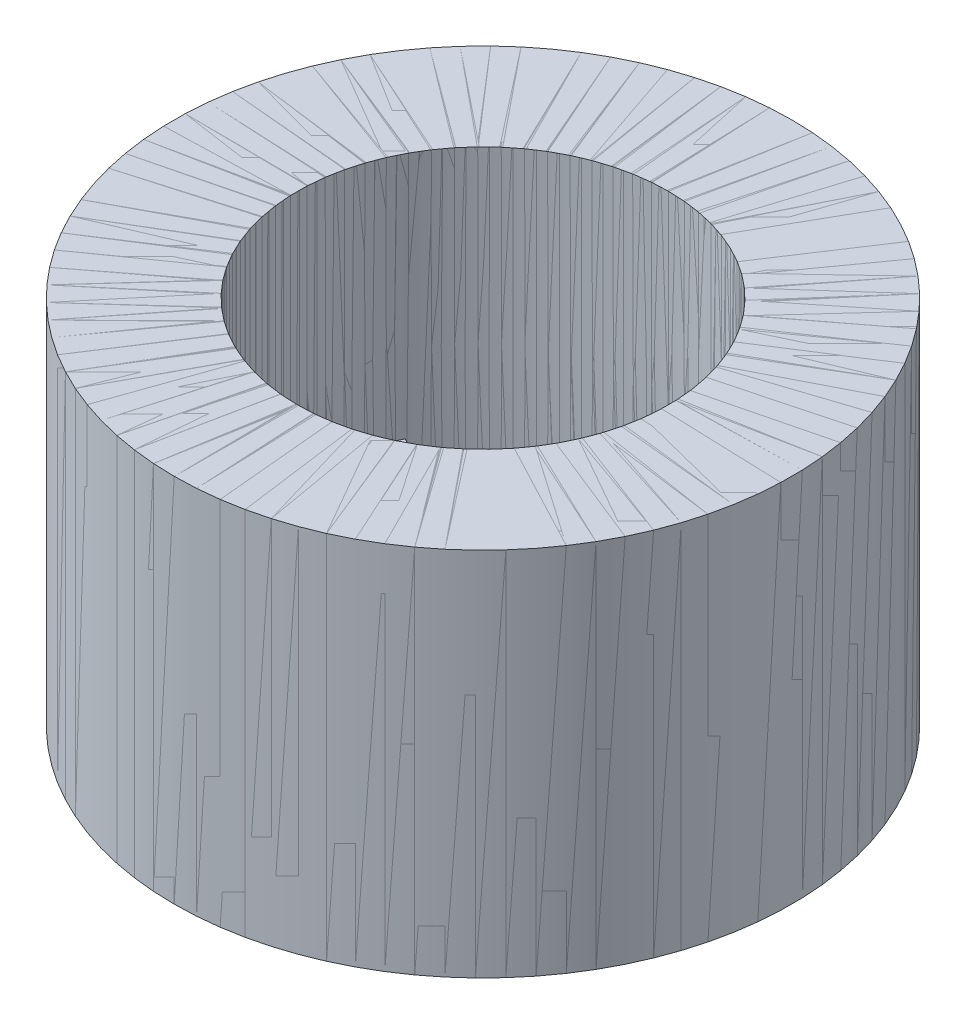
SolidWorks part; units mm, degrees
ref_plane "Front Plane" through (0, 0, 0) normal (0, 0, 1) x (1, 0, 0)
ref_plane "Top Plane" through (0, 0, 0) normal (0, 1, 0) x (1, 0, 0)
ref_plane "Right Plane" through (0, 0, 0) normal (1, 0, 0) x (0, 0, -1)
sketch "Sketch1" plane through (0, 0, 0) normal (0, 1, 0) x (1, 0, 0)
  line L2 (-2.5316, 14.7848) -> (-1.5, 9.2848)
  line L4 (1.451, 4.7848) -> (1.5, 9.2848)
  line L5 (1.5, 9.2848) -> (2.5316, 14.7848)
  line L6 (-1.5, 9.2848) -> (-1.451, 4.7848)
  line L7 (0, -55) -> (0, 55) construction
  circle A0 centre (0, 0) radius 15
  circle A1 centre (0, 0) radius 25
  arc A2 (-2.5316, 14.7848) -> (2.5316, 14.7848) centre (0, 0) cw
  circle A3 centre (0, 0) radius 5
  arc A4 (-1.451, 4.7848) -> (1.451, 4.7848) centre (0, 0) cw
  circle A5 centre (0, 0) radius 3
  dimension "D1" = 30
  dimension "D2" = 50
  dimension "D3" = 6
  dimension "D4" = 10
  dimension "D5" = 5
  dimension "D6" = 5.5
  dimension "D7" = 4.5
  dimension "D8" = 170
  dimension "D9" = 170
  dimension "D10" = 1.5
  dimension "D11" = 1.5
extrude "Boss-Extrude1" add sketch "Sketch1" along normal blind 30 contours A1 A0 region at (-24.2929, 0, 0)
extrude "Boss-Extrude3" add sketch "Sketch1<4>" along normal blind 10 contours A3 L4 L5 A0 L2 L6 region at (0, 0, -10.4697)
sketch "Sketch1<4>" plane through (0, 0, 0) normal (0, 1, 0) x (1, 0, 0) same geometry as "Sketch1"
extrude "Boss-Extrude2" add sketch "Sketch1<3>" along normal blind 10 separate body contours A4 L6 A3 A5 region at (0, 0, -4.8586)
sketch "Sketch1<3>" plane through (0, 0, 0) normal (0, 1, 0) x (1, 0, 0) same geometry as "Sketch1"
pattern_circular "CirPattern7" count 5 over 360 about axis through (0, 0, 0) along (0, 1, 0) of bodies 111
ref_plane "Plane1" through (0, 80, 0) normal (0, 1, 0) x (1, 0, 0)
